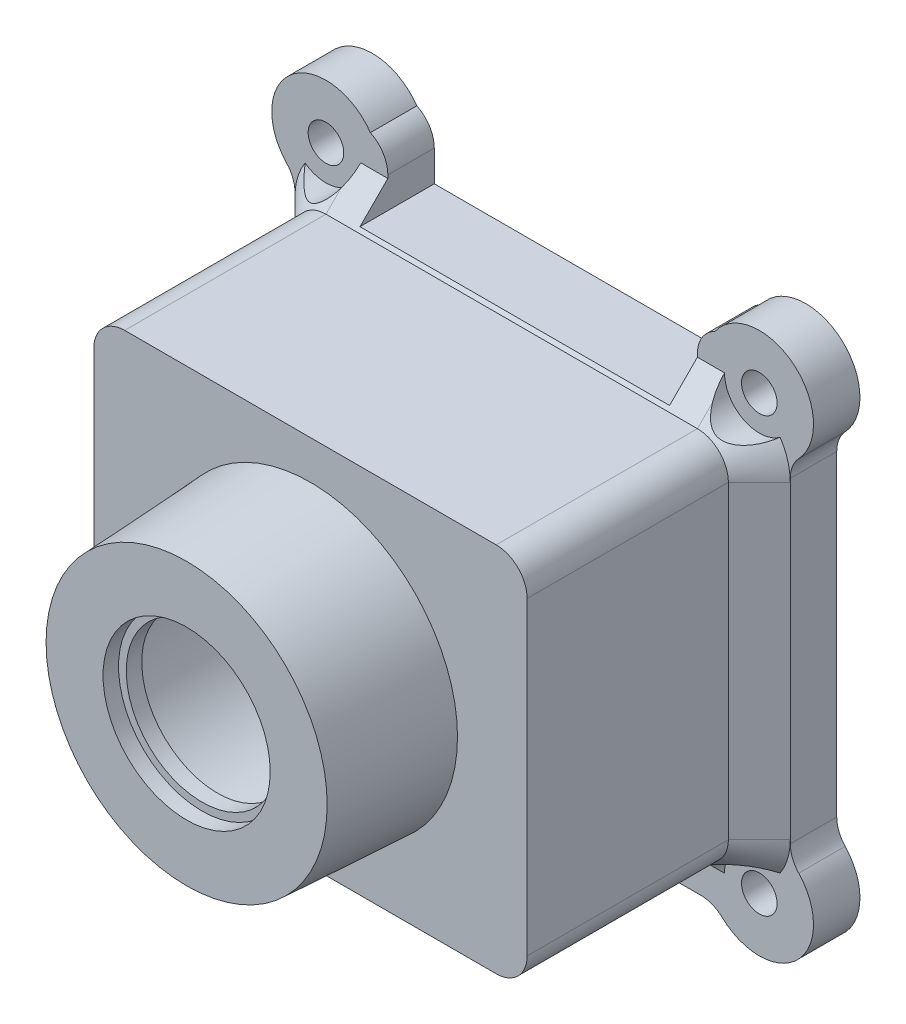
SolidWorks part; units mm, degrees
material "PLA"
ref_plane "前视基准面" through (0, 0, 0) normal (0, 0, 1) x (1, 0, 0)
ref_plane "上视基准面" through (0, 0, 0) normal (0, 1, 0) x (1, 0, 0)
ref_plane "右视基准面" through (0, 0, 0) normal (1, 0, 0) x (0, 0, -1)
sketch "草图1" plane through (0, 0, 0) normal (0, 0, 1) x (1, 0, 0)
  line L1 (-12, -10) -> (12, -10)
  line L2 (-12, -10) -> (-12, 10)
  line L3 (-12, 10) -> (12, 10)
  line L4 (12, -10) -> (12, 10)
  line L5 (-12, -10) -> (12, 10) construction
  line L6 (-12, 10) -> (12, -10) construction
  line L7 (-14, -12) -> (14, -12)
  line L8 (-14, -12) -> (-14, 12)
  line L9 (-14, 12) -> (14, 12)
  line L10 (14, -12) -> (14, 12)
  line L11 (-14, -12) -> (14, 12) construction
  line L12 (-14, 12) -> (14, -12) construction
  point P0 (0, 0)
  point P6 (0, 0)
  dimension "D1" = 24
  dimension "D2" = 20
  dimension "D3" = 2
  dimension "D4" = 2
extrude "凸台-拉伸1" add sketch "草图1" along normal blind 16
sketch "草图2" plane through (0, 0, 0) normal (0, 0, -1) x (-1, 0, 0)
  line L1 (-16, -16) -> (16, -16)
  line L2 (-16, -16) -> (-16, 16)
  line L3 (-16, 16) -> (16, 16)
  line L4 (16, -16) -> (16, 16)
  line L5 (-16, -16) -> (16, 16) construction
  line L6 (-16, 16) -> (16, -16) construction
  line L7 (-14, -14) -> (14, -14) construction
  line L8 (-14, -14) -> (-14, 14) construction
  line L9 (-14, 14) -> (14, 14) construction
  line L10 (14, -14) -> (14, 14) construction
  line L11 (-14, -14) -> (14, 14) construction
  line L12 (-14, 14) -> (14, -14) construction
  circle A0 centre (-14, 14) radius 1.15
  circle A1 centre (-14, -14) radius 1.15
  circle A2 centre (14, -14) radius 1.15
  circle A3 centre (14, 14) radius 1.15
  point P0 (0, 0)
  point P6 (0, 0)
  line M7 (-14, 12) -> (-14, -12)
  line M8 (-14, -12) -> (14, -12)
  line M9 (14, -12) -> (14, 12)
  line M10 (14, 12) -> (-14, 12)
  dimension "D3" = 2.3
  dimension "D1" = 28
  dimension "D2" = 28
  dimension "D4" = 2
extrude "凸台-拉伸2" add sketch "草图2" against normal blind 3 contours L1 L4 L3 L2 A3 A2 A1 A0 M7 M10 M9 M8 region at (15.5475, 0, 0)
sketch "草图3" plane through (0, 0, 16) normal (0, 0, 1) x (1, 0, 0)
  line L1 (-14, 12) -> (14, 12)
  line L2 (-14, 12) -> (-14, -12)
  line L3 (-14, -12) -> (14, -12)
  line L4 (14, 12) -> (14, -12)
  circle A0 centre (0, 0) radius 7.25
  dimension "D1" = 14.5
extrude "凸台-拉伸3" add sketch "草图3" along normal blind 2
sketch "草图4" plane through (0, 0, 18) normal (0, 0, 1) x (1, 0, 0)
  circle A1 centre (0, 0) radius 9.5
  dimension "D1" = 19
extrude "凸台-拉伸4" add sketch "草图4" along normal blind 8 draft 3
sketch "草图6" plane through (0, 0, 18) normal (0, 0, -1) x (-1, 0, 0)
  circle A1 centre (0, 0) radius 7.25
  circle A2 centre (0, 0) radius 7.25 construction
extrude "切除-拉伸2" cut sketch "草图6" against normal through all
sketch "草图5" plane through (0, 0, 26) normal (0, 0, 1) x (1, 0, 0)
  circle A0 centre (0, 0) radius 4.9
  circle A1 centre (0, 0) radius 7.25
  circle A2 centre (0, 0) radius 7.25 construction
  dimension "D1" = 9.8
extrude "凸台-拉伸5" add sketch "草图5" against normal blind 2
sketch "草图9" plane through (0, 0, 26) normal (0, 0, 1) x (1, 0, 0)
  circle A0 centre (0, 0) radius 5.4
  dimension "D1" = 10.8
extrude "切除-拉伸5" cut sketch "草图9" against normal blind 1
fillet "圆角1" radius 2 8 edges at (-12, -10, 8) (12, -10, 8) (12, 10, 8) (-12, 10, 8) (-14, -12, 10.5) (-14, 12, 10.5) (14, -12, 10.5) (14, 12, 10.5)
sketch "草图7" plane through (0, 0, 0) normal (0, 0, -1) x (-1, 0, 0)
  line L0 (0, 0) -> (0, 19.1924) construction
  line L1 (10, 17.2) -> (-10, 17.2)
  line L2 (10, 17.2) -> (10, 12.2)
  line L3 (10, 12.2) -> (-10, 12.2)
  line L4 (-10, 17.2) -> (-10, 12.2)
  line L5 (10, 17.2) -> (-10, 12.2) construction
  line L6 (10, 12.2) -> (-10, 17.2) construction
  point P0 (0, 14.7)
  dimension "D1" = 20
  dimension "D2" = 12.2
  dimension "D4" = 5
extrude "切除-拉伸3" cut sketch "草图7" against normal up to next
chamfer "倒角1" distance 2 angle 45 8 edges at (0, 12, 3) (13.4142, 11.4142, 3) (-13.4142, 11.4142, 3) (14, 0, 3) (-14, 0, 3) (13.4142, -11.4142, 3) (-13.4142, -11.4142, 3) (0, -12, 3)
sketch "草图8" plane through (0, 0, 3) normal (0, 0, 1) x (1, 0, 0)
  circle A0 centre (-14, -14) radius 2.25
  circle A1 centre (14, -14) radius 2.25
  circle A2 centre (14, 14) radius 2.25
  circle A3 centre (-14, 14) radius 2.25
  dimension "D1" = 4.5
extrude "切除-拉伸4" cut sketch "草图8" along normal blind 10
sketch "草图10" plane through (0, 0, 3) normal (0, 0, 1) x (1, 0, 0)
  line L0 (16, -16) -> (16, -11.1277)
  line L1 (16, -16) -> (16, -10) construction
  line L2 (16, -16) -> (-16, -16) construction
  line L3 (16, -16) -> (11.1277, -16)
  line L4 (0, 0) -> (0, -4.1181) construction
  line L5 (0, 0) -> (-3.5705, 0) construction
  line L6 (-16, -16) -> (-11.1277, -16)
  line L7 (-16, -16) -> (-16, -11.1277)
  line L8 (-16, 16) -> (-11.1277, 16)
  line L9 (-16, 16) -> (-16, 11.1277)
  line L10 (16, 16) -> (11.1277, 16)
  line L11 (16, 16) -> (16, 11.1277)
  arc A0 (11.1277, -16) -> (16, -11.1277) centre (14, -14) ccw
  arc A1 (-11.1277, -16) -> (-16, -11.1277) centre (-14, -14) cw
  arc A2 (-11.1277, 16) -> (-16, 11.1277) centre (-14, 14) ccw
  arc A3 (11.1277, 16) -> (16, 11.1277) centre (14, 14) cw
  dimension "D1" = 7
extrude "凸台-拉伸6" add sketch "草图10" against normal up to surface (3 mm away) up to face at (0, 7.05, 0)
fillet "圆角2" radius 2 8 edges at (16, -11.1277, 1.5) (11.1277, -16, 1.5) (-11.1277, -16, 1.5) (-16, 11.1277, 1.5) (-16, -11.1277, 1.5) (-10, 16, 1.5) (10, 16, 1.5) (16, 11.1277, 1.5)
